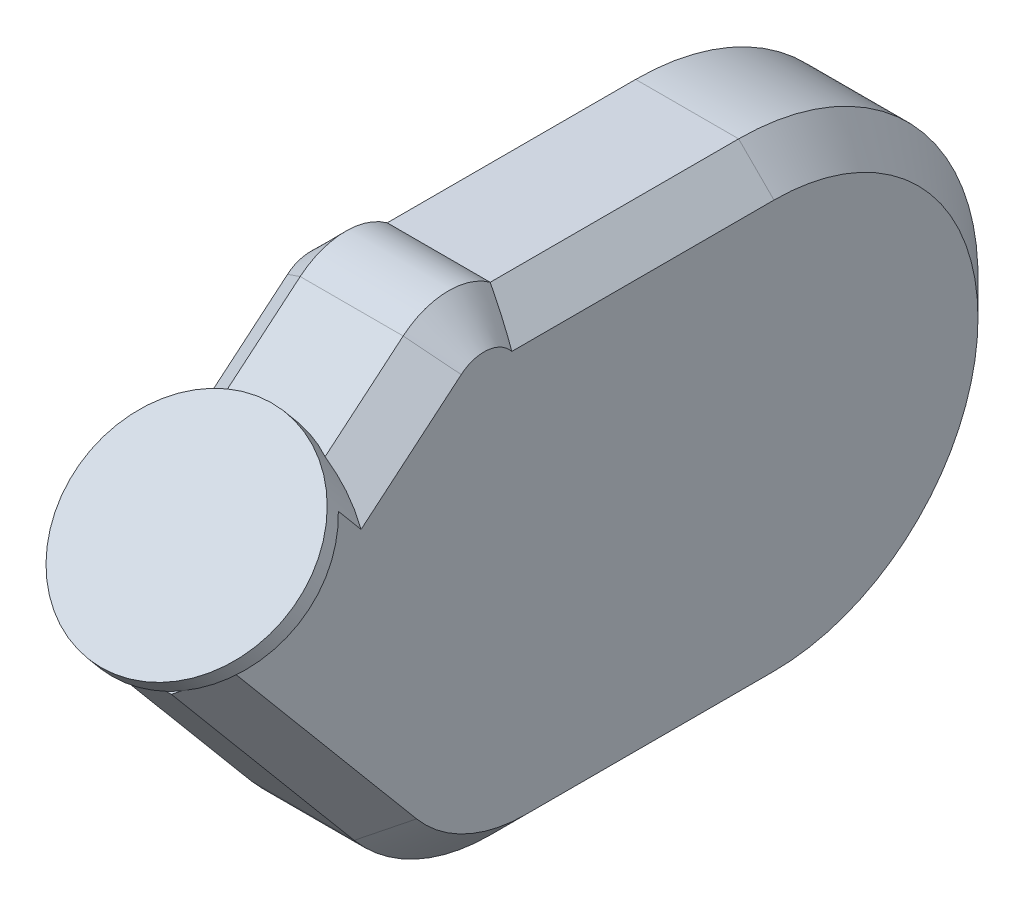
SolidWorks part; units mm, degrees
ref_plane "Front Plane" through (0, 0, 0) normal (0, 0, 1) x (1, 0, 0)
ref_plane "Top Plane" through (0, 0, 0) normal (0, 1, 0) x (1, 0, 0)
ref_plane "Right Plane" through (0, 0, 0) normal (1, 0, 0) x (0, 0, -1)
sketch "Sketch1" plane through (0, 0, 0) normal (0, 0, 1) x (1, 0, 0)
  line L1 (3.12, 8.6) -> (-3.12, 8.6)
  line L2 (3.12, 8.6) -> (3.12, -8.6)
  line L3 (3.12, -8.6) -> (-3.12, -8.6)
  line L4 (-3.12, 8.6) -> (-3.12, -8.6)
  line L5 (3.12, 8.6) -> (-3.12, -8.6) construction
  line L6 (3.12, -8.6) -> (-3.12, 8.6) construction
  point P0 (0, 0)
  dimension "D1" = 17.2
  dimension "D2" = 6.24
extrude "Extrude1" add sketch "Sketch1" along normal blind 17.526
fillet "Fillet1" 2 edges at (0, 8.6, 0) (0, -8.6, 0) type full round first side face at (0, 8.6, 8.763) second side face at (0, -8.6, 8.763) middle face at (0, 0, 0)
sketch "Sketch2" plane through (-3.12, 0, 0) normal (-1, 0, 0) x (0, 0, 1)
  line L0 (17.526, -8.6) -> (17.526, 8.6)
  line L1 (17.526, 8.6) -> (17.526, -8.6) construction
  line L2 (22.4138, -6.3208) -> (28.9803, 1.5049)
  line L3 (28.9803, 1.5049) -> (18.765, 10.0766)
  line L4 (18.765, 10.0766) -> (17.526, 8.6)
  arc A0 (17.526, -8.6) -> (22.4138, -6.3208) centre (17.526, -2.2194) ccw
  dimension "D2" = 6.3806
  dimension "D1" = 40
  dimension "D3" = 1.9275
extrude "Extrude2" add sketch "Sketch2" against normal up to surface (6.24 mm away) up to face at (3.12, 0, 10.913)
sketch "Sketch3" plane through (0, 15.8124, 11.9294) normal (0, 0.766, 0.6428) x (1, 0, 0)
  circle A0 centre (0, -18.6074) radius 4.0107
extrude "Extrude3" add sketch "Sketch3" along normal blind 0.6232
fillet "Fillet2" radius 2.54 1 edges at (0, 10.0766, 18.765)
chamfer "Chamfer1" distance 1.27 angle 45 14 edges at (3.12, -2.4079, 25.6971) (3.12, -8.0022, 20.2225) (3.12, -8.6, 13.063) (3.12, 0, 0) (3.12, 8.6, 13.063) (-3.12, -2.4079, 25.6971) (-3.12, -8.0022, 20.2225) (-3.12, -8.6, 13.063) (-3.12, 0, 0) (-3.12, 8.6, 13.063) (3.12, 6.9819, 22.4531) (3.12, 9.0848, 19.1083) (-3.12, 6.9819, 22.4531) (-3.12, 9.0848, 19.1083)
